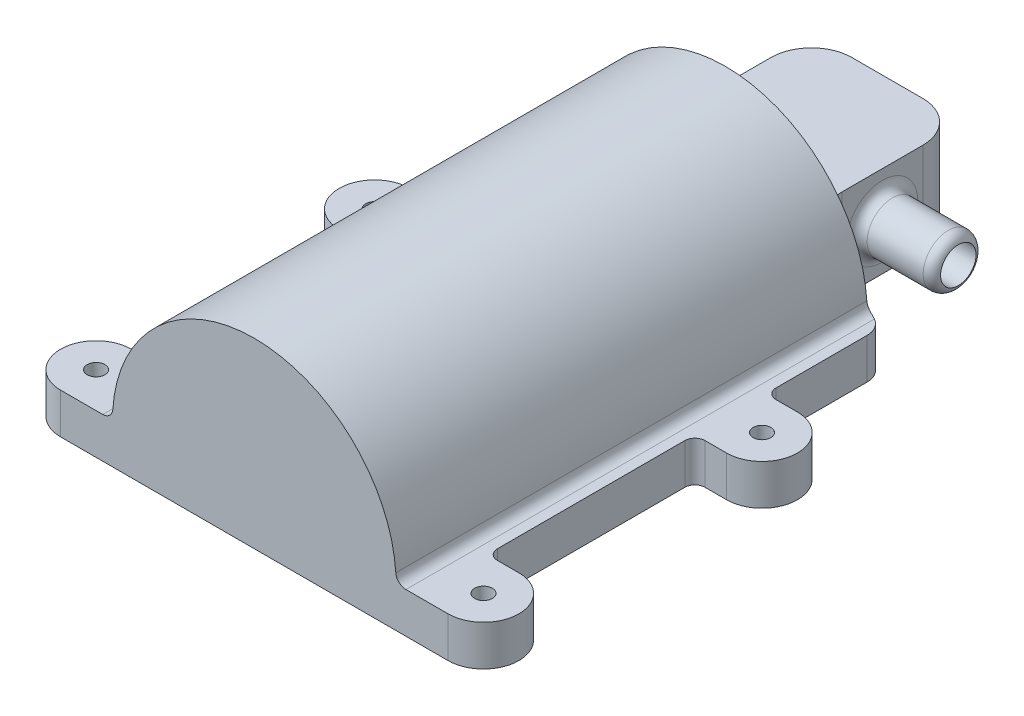
SolidWorks part; units mm, degrees
ref_plane "前视基准面" through (0, 0, 0) normal (0, 0, 1) x (1, 0, 0)
ref_plane "上视基准面" through (0, 0, 0) normal (0, 1, 0) x (1, 0, 0)
ref_plane "右视基准面" through (0, 0, 0) normal (1, 0, 0) x (0, 0, -1)
other "Configuration Table"
sketch "草图1" plane through (0, 0, 0) normal (0, 1, 0) x (1, 0, 0)
  line L0 (0, 49.8731) -> (0, -34.845) construction
  line L1 (0, 0) -> (-73.4019, 0) construction
  line L2 (-38.25, 34.5) -> (-34, 34.5)
  line L3 (-38.25, -34.5) -> (38.25, -34.5)
  line L4 (-32, 36.5) -> (-32, 54.5)
  line L5 (-28, 58.5) -> (-23, 58.5)
  line L6 (-15, 66.5) -> (-15, 82.5)
  line L7 (-7, 90.5) -> (7, 90.5)
  line L8 (15, 66.5) -> (15, 82.5)
  line L9 (28, 58.5) -> (23, 58.5)
  line L10 (32, 36.5) -> (32, 54.5)
  line L11 (38.25, 34.5) -> (34, 34.5)
  line L12 (-38.25, 20.5) -> (-34, 20.5)
  line L13 (-32, 18.5) -> (-32, -18.5)
  line L14 (38.25, 20.5) -> (34, 20.5)
  line L15 (32, 18.5) -> (32, -18.5)
  line L16 (38.25, -20.5) -> (34, -20.5)
  line L17 (-38.25, -20.5) -> (-34, -20.5)
  line L18 (-32, 18.5) -> (-32, 36.5)
  line L19 (32, 18.5) -> (32, 36.5)
  line L20 (-32, -18.5) -> (-32, -34.5)
  line L21 (32, -18.5) -> (32, -34.5)
  arc A0 (-38.25, 34.5) -> (-38.25, 20.5) centre (-38.25, 27.5) ccw
  arc A1 (38.25, 34.5) -> (38.25, 20.5) centre (38.25, 27.5) cw
  arc A2 (38.25, -34.5) -> (38.25, -20.5) centre (38.25, -27.5) ccw
  arc A3 (-38.25, -34.5) -> (-38.25, -20.5) centre (-38.25, -27.5) cw
  arc A4 (-34, 34.5) -> (-32, 36.5) centre (-34, 36.5) ccw
  arc A5 (-32, 54.5) -> (-28, 58.5) centre (-28, 54.5) cw
  arc A6 (-15, 82.5) -> (-7, 90.5) centre (-7, 82.5) cw
  arc A7 (-23, 58.5) -> (-15, 66.5) centre (-23, 66.5) ccw
  arc A8 (15, 82.5) -> (7, 90.5) centre (7, 82.5) ccw
  arc A9 (23, 58.5) -> (15, 66.5) centre (23, 66.5) cw
  arc A10 (32, 54.5) -> (28, 58.5) centre (28, 54.5) ccw
  arc A11 (34, 34.5) -> (32, 36.5) centre (34, 36.5) cw
  arc A12 (-34, 20.5) -> (-32, 18.5) centre (-34, 18.5) cw
  arc A13 (34, 20.5) -> (32, 18.5) centre (34, 18.5) ccw
  arc A14 (34, -20.5) -> (32, -18.5) centre (34, -18.5) cw
  arc A15 (-34, -20.5) -> (-32, -18.5) centre (-34, -18.5) ccw
  point P24 (-32, 34.5)
  point P27 (-32, 58.5)
  point P30 (-15, 90.5)
  point P33 (-15, 58.5)
  point P35 (0, 90.5)
  point P57 (32, 0)
  point P58 (-32, 0)
  dimension "D1" = 7
  dimension "D10" = 2
  dimension "D11" = 4
  dimension "D12" = 8
  dimension "D13" = 2
  dimension "D2" = 38.25
  dimension "D3" = 27.5
  dimension "D4" = 125
  dimension "D5" = 24
  dimension "D6" = 17
  dimension "D7" = 32
  dimension "D8" = 15
  dimension "D9" = 6.25
  dimension "D14" = 64
extrude "凸台-拉伸1" add sketch "草图1" along normal blind 8 contours L12 A12 L18 A4 L2 A0 | A15 L17 A3 L3 L20 | L16 A14 L21 L3 A2 | A13 L14 A1 L11 A11 L19 | L16 A14 L15 A13 L14 A1 L11 A11 L10 A10 L9 A9 L8 A8 L7 A6 L6 A7 L5 A5 L4 A4 L2 A0 L12 A12 L13 A15 L17 A3 L3 A2 region at (-37.9206, 0, -27.5) region at (-37.9491, 0, 27.4613) region at (37.9491, 0, 27.4613) region at (37.9206, 0, -27.5)
sketch "草图3" plane through (0, 8, 0) normal (0, 1, 0) x (1, 0, 0)
  circle A0 centre (-38.25, 27.5) radius 1.75
  circle A1 centre (38.25, 27.5) radius 1.75
  circle A2 centre (-38.25, -27.5) radius 1.75
  circle A3 centre (38.25, -27.5) radius 1.75
  dimension "D1" = 3.5
extrude "切除-拉伸1" cut sketch "草图3" against normal up to next
sketch "草图6" plane through (0, 0, 34.5) normal (0, 0, 1) x (1, 0, 0)
  line L0 (-38.25, 8) -> (38.25, 8) construction
  line L1 (-28, 8) -> (28, 8)
  arc A0 (-28, 8) -> (28, 8) centre (0, 8) cw
  dimension "D1" = 56
extrude "凸台-拉伸3" add sketch "草图6" against normal blind 93
sketch "草图7" plane through (0, 8, 0) normal (0, 1, 0) x (1, 0, 0)
  line L0 (23, 58.5) -> (-23, 58.5)
  line L1 (-15, 66.5) -> (-15, 82.5)
  line L2 (-7, 90.5) -> (7, 90.5)
  line L3 (15, 82.5) -> (15, 66.5)
  arc A0 (-23, 58.5) -> (-15, 66.5) centre (-23, 66.5) ccw
  arc A1 (-15, 82.5) -> (-7, 90.5) centre (-7, 82.5) cw
  arc A2 (7, 90.5) -> (15, 82.5) centre (7, 82.5) cw
  arc A3 (15, 66.5) -> (23, 58.5) centre (23, 66.5) ccw
extrude "凸台-拉伸4" add sketch "草图7" along normal blind 10
sketch "草图9" plane through (0, 0, 0) normal (1, 0, 0) x (0, 0, -1)
  line L0 (74.5, 18) -> (74.5, 0) construction
  line L1 (66.5, 18) -> (82.5, 18) construction
  line L2 (66.5, 0) -> (82.5, 0) construction
  circle A0 centre (74.5, 9) radius 5
  dimension "D1" = 10
extrude "凸台-拉伸6" add sketch "草图9" along normal mid plane 60
sketch "草图10" plane through (-30, 0, 0) normal (-1, 0, 0) x (0, 0, 1)
  circle A0 centre (-74.5, 9) radius 3.5
  dimension "D1" = 7
extrude "切除-拉伸2" cut sketch "草图10" against normal up to next
fillet "圆角1" radius 2 2 edges at (-30, 9, -79.5) (30, 9, -79.5)
fillet "圆角2" radius 2 3 edges at (28, 8, -12) (-28, 8, -12) (0, 18, -58.5)
ref_plane "基准面1" through (0, 0, 27.5) normal (0, 0, -1) x (-1, 0, 0)
fillet "圆角5" radius 2 2 edges at (15, 9, -69.5) (-15, 9, -69.5)
